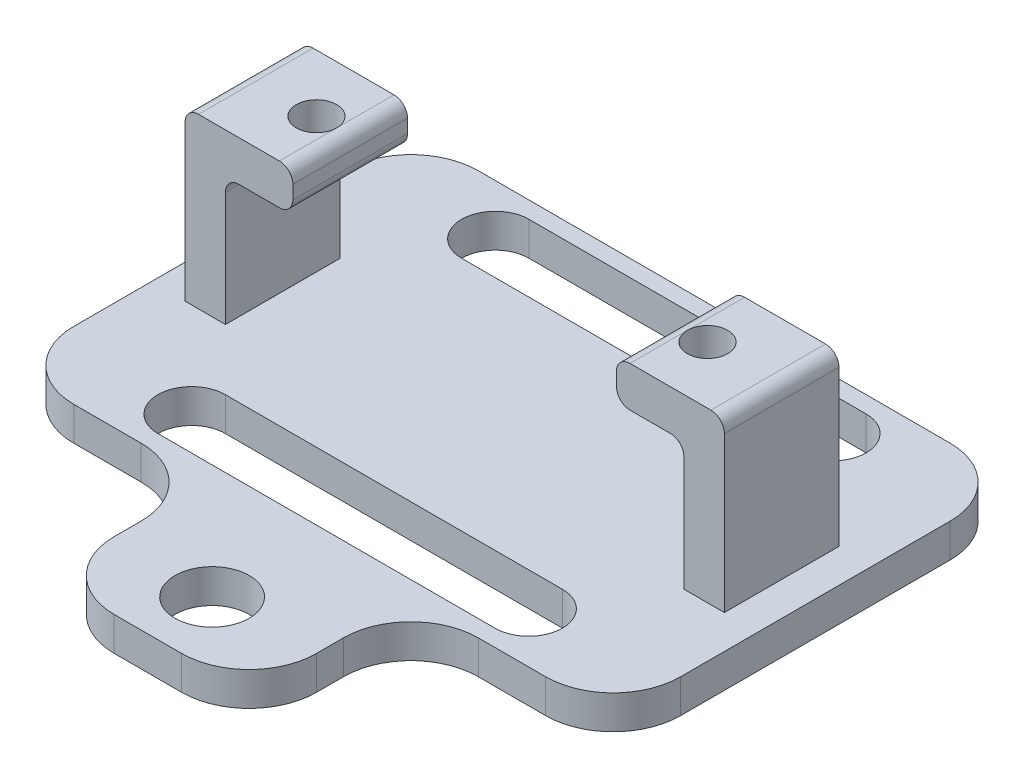
SolidWorks part; units mm, degrees
ref_plane "Front Plane" through (0, 0, 0) normal (0, 0, 1) x (1, 0, 0)
ref_plane "Top Plane" through (0, 0, 0) normal (0, 1, 0) x (1, 0, 0)
ref_plane "Right Plane" through (0, 0, 0) normal (1, 0, 0) x (0, 0, -1)
sketch "Sketch1" plane through (0, 0, 0) normal (0, 1, 0) x (1, 0, 0)
  line L0 (-35, -3.74) -> (-10, -3.74) construction
  line L1 (0, 0) -> (-30, 0)
  line L2 (0, 0) -> (0, -30)
  line L3 (0, -30) -> (-15, -30)
  line L4 (-45, 0) -> (-45, -30)
  line L5 (-35, -1.24) -> (-10, -1.24)
  line L6 (-35, -6.24) -> (-10, -6.24)
  line L7 (-35, -26.26) -> (-10, -26.26) construction
  line L8 (-35, -23.76) -> (-10, -23.76)
  line L9 (-35, -28.76) -> (-10, -28.76)
  line L10 (-35, -3.74) -> (-35, 0) construction
  line L11 (-35, -26.26) -> (-35, -30) construction
  line L12 (-35, -3.74) -> (-45, -3.74) construction
  line L13 (-10, -3.74) -> (0, -3.74) construction
  line L14 (-45, -15) -> (-35, -15) construction
  line L15 (-35, -15) -> (-35, -3.74) construction
  line L16 (-35, -15) -> (-35, -23.76) construction
  line L17 (-30, 0) -> (-45, 0)
  line L22 (-22.5, -37.24) -> (-22.5, -42) construction
  line L24 (-30, -30) -> (-30, -42)
  line L25 (-30, -42) -> (-15, -42)
  line L27 (-30, -30) -> (-45, -30)
  line L28 (-15, -42) -> (-15, -30)
  arc A0 (-35, -1.24) -> (-35, -6.24) centre (-35, -3.74) ccw
  arc A1 (-10, -6.24) -> (-10, -1.24) centre (-10, -3.74) ccw
  arc A2 (-35, -23.76) -> (-35, -28.76) centre (-35, -26.26) ccw
  arc A3 (-10, -28.76) -> (-10, -23.76) centre (-10, -26.26) ccw
  circle A5 centre (-22.5, -37.24) radius 2.75
  point P7 (-22.5, -3.74)
  point P12 (-22.5, -26.26)
  dimension "D3" = 2.5
  dimension "D6" = 7.24
  dimension "D9" = 5.5
  dimension "D1" = 45
  dimension "D2" = 30
  dimension "D4" = 11.26
  dimension "D5" = 10
  dimension "D7" = 12
extrude "Boss-Extrude1" add sketch "Sketch1" along normal blind 2.5
ref_plane "Plane1" through (-22.5, 0, 0) normal (1, 0, 0) x (0, 0, -1)
ref_plane "Plane2" through (0, 0, 15) normal (0, 0, 1) x (1, 0, 0)
sketch "Sketch3" plane through (0, 0, 15) normal (0, 0, 1) x (1, 0, 0)
  line L0 (-15, 2.5) -> (0, 2.5) construction
  line L1 (-39.5, 2.5) -> (-42.5, 2.5)
  line L2 (-39.5, 2.5) -> (-39.5, 12)
  line L4 (-42.5, 2.5) -> (-42.5, 12)
  line L5 (-39.5, 12) -> (-34.5, 12)
  line L18 (-34.5, 12) -> (-34.5, 15)
  line L19 (-34.5, 15) -> (-42.5, 15)
  line L20 (-42.5, 12) -> (-42.5, 15)
  line L22 (-22.5, -1.375) -> (-22.5, 1.375) construction
  dimension "D1" = 12.5
  dimension "D2" = 3
  dimension "D3" = 8
  dimension "D5" = 3
  dimension "D6" = 12
extrude "Boss-Extrude3" add sketch "Sketch3" along normal blind 4.25 and the other way blind 4.25
sketch "Sketch5" plane through (0, 15, 0) normal (0, 1, 0) x (1, 0, 0)
  line L0 (-37, -19.25) -> (-37, -15) construction
  line L1 (-34.5, -19.25) -> (-42.5, -19.25) construction
  line L2 (-37, -15) -> (-34.5, -15) construction
  line L5 (-34.5, -10.75) -> (-34.5, -19.25) construction
  circle A0 centre (-37, -15) radius 1.5
  dimension "D1" = 3
  dimension "D2" = 2.5
extrude "Cut-Extrude1" cut sketch "Sketch5" along direction (0, 1, 0) on the side against the normal blind 5 contours A0
fillet "Fillet1" radius 1 1 edges at (-39.5, 12, 15)
fillet "Fillet2" radius 1 1 edges at (-34.5, 12, 15)
fillet "Fillet3" radius 1 1 edges at (-34.5, 15, 15)
fillet "Fillet4" radius 1 1 edges at (-42.5, 15, 15)
mirror "Mirror1" about plane through (-22.5, 0, 0) normal (1, 0, 0) of "Fillet1", "Fillet2", "Fillet3", "Fillet4", "Boss-Extrude3", "Cut-Extrude1"
fillet "Fillet5" radius 5 2 edges at (-15, 1.25, 30) (-30, 1.25, 30)
fillet "Fillet6" radius 5 6 edges at (-45, 1.25, 30) (-45, 1.25, 0) (0, 1.25, 0) (0, 1.25, 30) (-30, 1.25, 42) (-15, 1.25, 42)
